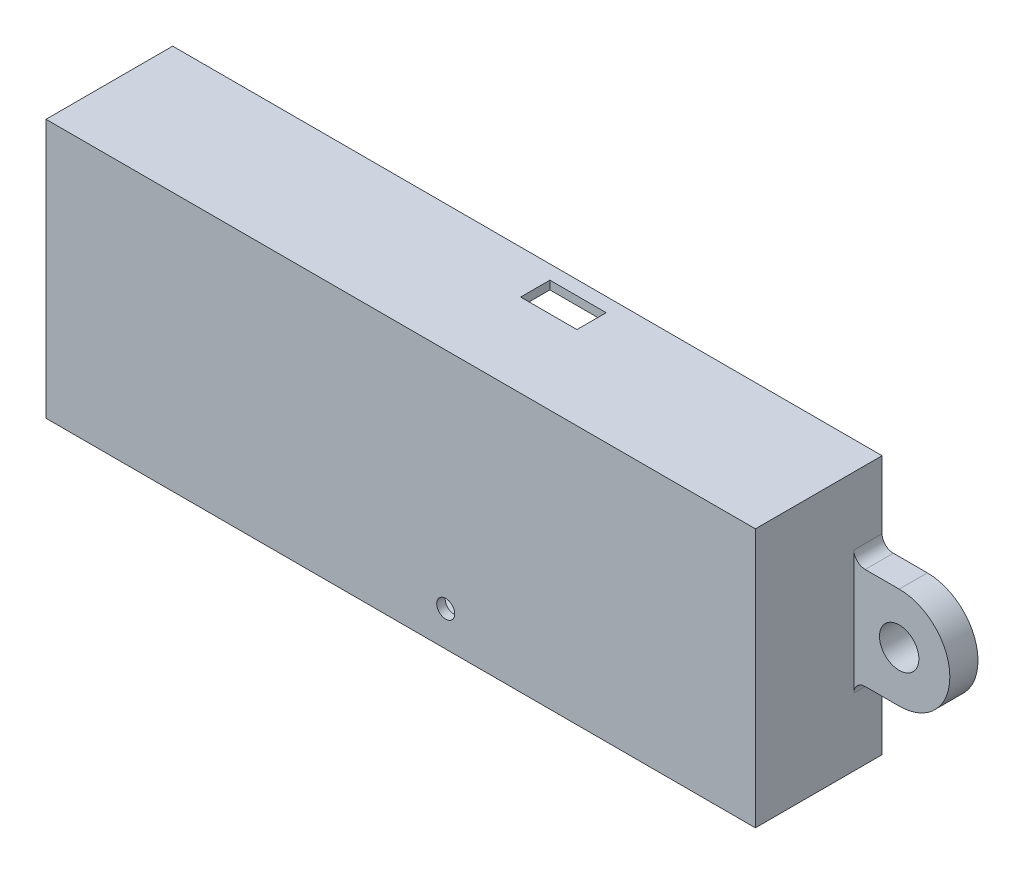
SolidWorks part; units mm, degrees
ref_plane "Спереди" through (0, 0, 0) normal (0, 0, 1) x (1, 0, 0)
ref_plane "Сверху" through (0, 0, 0) normal (0, 1, 0) x (1, 0, 0)
ref_plane "Справа" through (0, 0, 0) normal (1, 0, 0) x (0, 0, -1)
sketch "Эскиз1" plane through (0, 0, 0) normal (0, 0, 1) x (1, 0, 0)
  line L5 (0, 0) -> (123, 0)
  line L6 (0, 0) -> (0, 43)
  line L7 (0, 43) -> (123, 43)
  line L8 (123, 0) -> (123, 43)
  dimension "D1" = 123
  dimension "D2" = 43
extrude "Бобышка-Вытянуть1" add sketch "Эскиз1" along normal blind 1.5
sketch "Эскиз2" plane through (0, 0, 0) normal (0, 0, -1) x (-1, 0, 0)
  line L1 (-124.5, -1.5) -> (1.5, -1.5)
  line L2 (-124.5, -1.5) -> (-124.5, 44.5)
  line L3 (-124.5, 44.5) -> (1.5, 44.5)
  line L4 (1.5, -1.5) -> (1.5, 44.5)
  line L9 (-123, 0) -> (0, 0)
  line L10 (-123, 0) -> (-123, 43)
  line L11 (-123, 43) -> (0, 43)
  line L12 (0, 0) -> (0, 43)
  dimension "D1" = 1.5
  dimension "D2" = 1.5
  dimension "D3" = 1.5
  dimension "D4" = 1.5
extrude "Бобышка-Вытянуть2" add sketch "Эскиз2" along normal blind 21 and the other way blind 1.5
sketch "Эскиз3" plane through (0, 0, -21) normal (0, 0, -1) x (-1, 0, 0)
  line L0 (-124.5, 12.5) -> (-132.54, 12.5)
  line L1 (-124.5, 30.5) -> (-132.54, 30.5)
  line L2 (-134.7332, 21.5) -> (-136.04, 21.5) construction
  line L3 (-124.5, 30.5) -> (-124.5, 12.5)
  line L4 (-123, 21.5) -> (0, 21.5) construction
  line L5 (-123, 43) -> (-123, 0) construction
  line L6 (0, 0) -> (0, 43) construction
  line L7 (-124.5, 44.5) -> (-124.5, -1.5) construction
  arc A0 (-132.54, 12.5) -> (-132.54, 30.5) centre (-132.54, 21.5) cw
  circle A1 centre (-132.54, 21.5) radius 3.5
  dimension "D1" = 7
  dimension "D3" = 9
  dimension "D2" = 9
  dimension "D4" = 8.04
extrude "Бобышка-Вытянуть3" add sketch "Эскиз3" against normal blind 5
ref_plane "Плоскость1" through (61.5, 0, 0) normal (1, 0, 0) x (0, 0, -1)
mirror "Зеркальное отражение1" about plane through (61.5, 0, 0) normal (1, 0, 0) of "Бобышка-Вытянуть3"
ref_plane "Плоскость2" through (123, 43, -21) normal (0, 0, -1) x (-1, 0, 0)
sketch "Эскиз5" plane through (0, 0, 1.5) normal (0, 0, 1) x (1, 0, 0)
  circle A0 centre (69.5, 4.7) radius 1.6
  dimension "D5" = 3.2
  dimension "D6" = 55
  dimension "D7" = 6.2
extrude "Вырез-Вытянуть1" cut sketch "Эскиз5" against normal blind 10
sketch "Эскиз6" plane through (-1.5, 0, 0) normal (-1, 0, 0) x (0, 0, 1)
  line L0 (-11, 17.3) -> (-16, 17.3)
  line L6 (-16, 9.65) -> (-16, 16.65)
  line L8 (-11, 8.5) -> (-11, 17.3)
  line L11 (-11, 8.5) -> (-16, 8.5)
  line L15 (-16, 17.3) -> (-16, 16.65)
  line L16 (-16, 9.65) -> (-16, 8.5)
  line L17 (1.5, -1.5) -> (-21, -1.5) construction
  line L18 (-21, -1.5) -> (-21, 12.5) construction
  dimension "D2" = 8.8
  dimension "D3" = 5
  dimension "D5" = 10
  dimension "D6" = 5
extrude "Вырез-Вытянуть2" cut sketch "Эскиз6" against normal blind 10
sketch "Эскиз7" plane through (0, 44.5, 0) normal (0, 1, 0) x (1, 0, 0)
  line L0 (-1.5, -1.5) -> (-1.5, 21) construction
  line L1 (48.5, 3.5) -> (63, 3.5)
  line L2 (48.5, 3.5) -> (48.5, 12.5)
  line L3 (48.5, 12.5) -> (63, 12.5)
  line L4 (63, 3.5) -> (63, 12.5)
  line L5 (-1.5, -1.5) -> (124.5, -1.5) construction
  dimension "D1" = 14.5
  dimension "D2" = 9
  dimension "D3" = 50
  dimension "D4" = 5
fillet "Скругление1" radius 2 4 edges at (124.5, 12.5, -18.5) (124.5, 30.5, -18.5) (-1.5, 30.5, -18.5) (-1.5, 12.5, -18.5)
sketch "Эскиз8" plane through (0, -1.5, 0) normal (0, -1, 0) x (1, 0, 0)
  line L0 (48.5, -3.5) -> (63, -3.5)
  line L1 (63, -3.5) -> (63, -12.5)
  line L2 (63, -12.5) -> (48.5, -12.5)
  line L3 (48.5, -12.5) -> (48.5, -3.5)
extrude "Вырез-Вытянуть4" cut sketch "Эскиз8" against normal blind 10
sketch "Эскиз10" plane through (0, 44.5, 0) normal (0, 1, 0) x (1, 0, 0)
  line L0 (124.5, -1.5) -> (124.5, 21) construction
  line L1 (78, 18.5) -> (68, 18.5)
  line L2 (78, 18.5) -> (78, 13.3)
  line L3 (78, 13.3) -> (68, 13.3)
  line L4 (68, 18.5) -> (68, 13.3)
  dimension "D1" = 46.5
  dimension "D2" = 10
  dimension "D3" = 5.2
  dimension "D4" = 2.5
extrude "Вырез-Вытянуть5" cut sketch "Эскиз10" against normal blind 10
